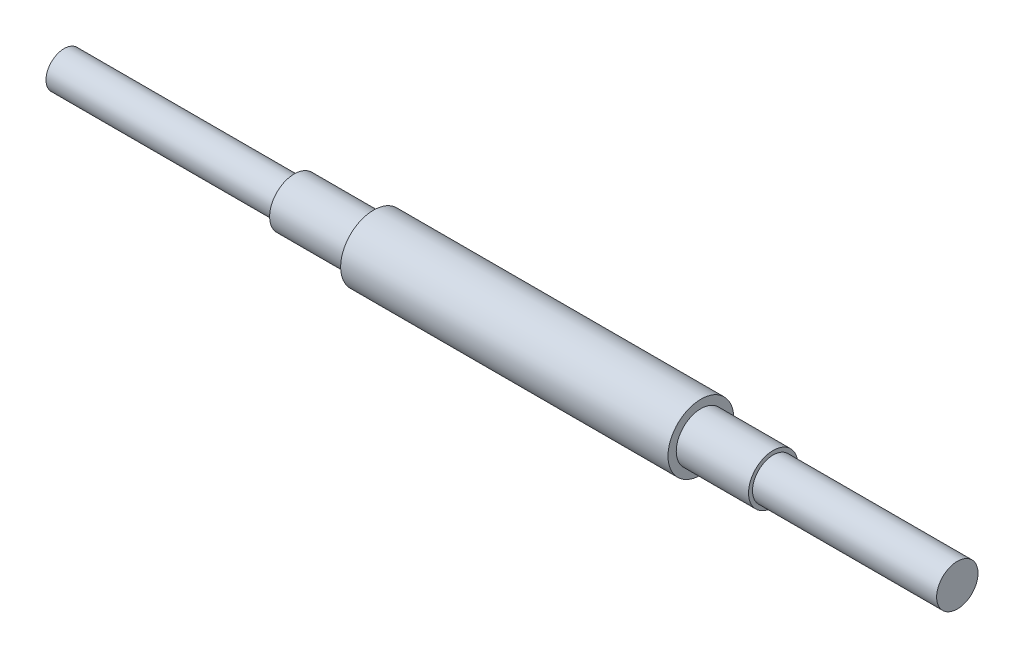
SolidWorks part; units mm, degrees
ref_plane "Front Plane" through (0, 0, 0) normal (0, 0, 1) x (1, 0, 0)
ref_plane "Top Plane" through (0, 0, 0) normal (0, 1, 0) x (1, 0, 0)
ref_plane "Right Plane" through (0, 0, 0) normal (1, 0, 0) x (0, 0, -1)
sketch "Sketch1" plane through (0, 0, 0) normal (0, 1, 0) x (1, 0, 0)
  line L0 (-78.6306, 0) -> (93.8678, 0) construction
  line L1 (-78.6306, 0) -> (-78.6306, 3.5)
  line L2 (-78.6306, 3.5) -> (-34.1806, 3.5)
  line L3 (-34.1806, 3.5) -> (-34.1806, 4.7625)
  line L4 (-34.1806, 4.7625) -> (-18.8815, 4.7625)
  line L5 (-18.8815, 4.7625) -> (-18.8815, 6.35)
  line L6 (-18.8815, 6.35) -> (44.3442, 6.35)
  line L7 (44.3442, 6.35) -> (44.3442, 4.7625)
  line L8 (44.3442, 4.7625) -> (58.3078, 4.7625)
  line L9 (58.3078, 4.7625) -> (58.3078, 3.9992)
  line L10 (58.3078, 3.9992) -> (93.8678, 3.9992)
  line L11 (93.8678, 3.9992) -> (93.8678, 0)
  line L12 (-78.6306, 0) -> (93.8678, 0)
  line L13 (-97.9506, 0) -> (194.5593, 0) construction
  point P15 (0, 0)
  dimension "D1" = 7
  dimension "D2" = 9.525
  dimension "D3" = 9.525
  dimension "D4" = 7.9985
  dimension "D5" = 44.45
  dimension "D6" = 15.2991
  dimension "D7" = 13.9636
  dimension "D8" = 35.56
  dimension "D9" = 63.2257
  dimension "D10" = 6.35
revolve "Revolve1" add sketch "Sketch1" angle 360 about L13
